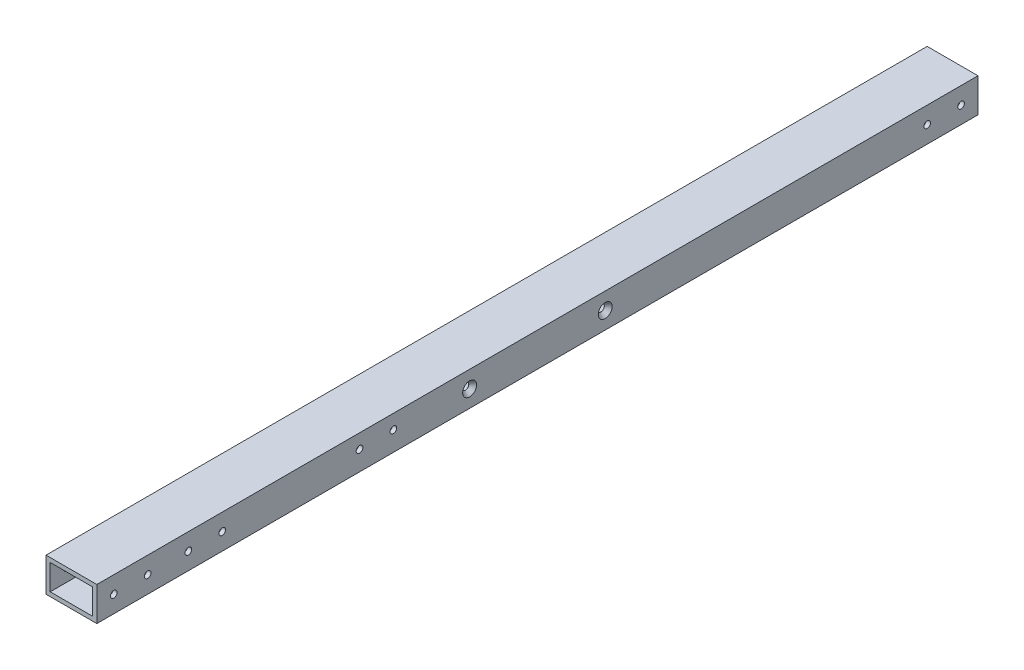
SolidWorks part; units mm, degrees
material "1060 Alloy"
ref_plane "Front Plane" through (0, 0, 0) normal (0, 0, 1) x (1, 0, 0)
ref_plane "Top Plane" through (0, 0, 0) normal (0, 1, 0) x (1, 0, 0)
ref_plane "Right Plane" through (0, 0, 0) normal (1, 0, 0) x (0, 0, -1)
sketch "Sketch1" plane through (0, 0, 0) normal (0, 0, 1) x (1, 0, 0)
  line L0 (-15.875, 9.525) -> (15.875, 9.525)
  line L2 (-19.05, 12.7) -> (19.05, 12.7)
  line L3 (-19.05, 12.7) -> (-19.05, -12.7)
  line L4 (-19.05, -12.7) -> (19.05, -12.7)
  line L5 (19.05, 12.7) -> (19.05, -12.7)
  line L10 (15.875, 9.525) -> (15.875, -9.525)
  line L11 (-15.875, -9.525) -> (15.875, -9.525)
  line L12 (-15.875, 9.525) -> (-15.875, -9.525)
  point P12 (0, 12.7)
  point P14 (19.05, 0)
  dimension "Wall Thickness" = 3.175
  dimension "Outside Width" = 38.1
  dimension "Outside Height" = 25.4
  dimension "Inside Height" = 19.05
  dimension "Inside Width" = 31.75
sketch "Sketch2" plane through (0, 0, 0) normal (1, 0, 0) x (0, 0, -1)
  line L0 (330.2, 0) -> (-330.2, 0)
  point P4 (0, 0)
  point P7 (-330.2, 0)
  point P10 (330.2, 0)
  dimension "Length" = 660.4
sketch "Sketch3" plane through (0, 0, 0) normal (0, 0, 1) x (1, 0, 0)
  line L21 (19.05, 12.7) -> (-19.05, 12.7)
  line L22 (19.05, -12.7) -> (19.05, 12.7)
  line L23 (-19.05, -12.7) -> (19.05, -12.7)
  line L24 (-19.05, 12.7) -> (-19.05, -12.7)
  line L25 (19.05, 12.7) -> (-19.05, 12.7)
  line L26 (19.05, -12.7) -> (19.05, 12.7)
  line L27 (-19.05, -12.7) -> (19.05, -12.7)
  line L28 (-19.05, 12.7) -> (-19.05, -12.7)
  line L29 (15.875, 9.525) -> (-15.875, 9.525)
  line L30 (15.875, -9.525) -> (15.875, 9.525)
  line L31 (-15.875, -9.525) -> (15.875, -9.525)
  line L32 (-15.875, 9.525) -> (-15.875, -9.525)
  line L33 (15.875, 9.525) -> (-15.875, 9.525)
  line L34 (15.875, -9.525) -> (15.875, 9.525)
  line L35 (-15.875, -9.525) -> (15.875, -9.525)
  line L36 (-15.875, 9.525) -> (-15.875, -9.525)
  dimension "D1" = 0
  dimension "D2" = 0
extrude "Boss-Extrude1" add sketch "Sketch3" along normal up to vertex (330.2 mm away) and the other way up to vertex (330.2 mm away) up to point (0, 0, 330.2) other way up to point (0, 0, -330.2)
sketch "Drawing Reference" plane through (0, 0, 0) normal (1, 0, 0) x (0, 0, -1)
  line L0 (-330.2, 0) -> (330.2, 0) construction
  line L1 (0, -12.7) -> (0, 12.7) construction
  line L2 (-330.2, -12.7) -> (330.2, -12.7) construction
  line L5 (-330.2, 12.7) -> (330.2, 12.7) construction
  point P7 (-302.768, 0)
  point P8 (302.768, 0)
  dimension "D1" = 27.432
sketch "Sketch4" plane through (-19.05, 0, 0) normal (-1, 0, 0) x (0, 0, 1)
  line L0 (-330.2, 0) -> (-317.5, 0)
  line L1 (-330.2, 12.7) -> (-330.2, -12.7) construction
  line L2 (-317.5, 0) -> (-292.1, 0)
  line L3 (330.2, 12.7) -> (330.2, -12.7) construction
  line L4 (330.2, 0) -> (317.5, 0)
  line L5 (317.5, 0) -> (292.1, 0)
  line L6 (0, 0) -> (50.8, 0) construction
  line L7 (0, 0) -> (-50.8, 0) construction
  point P11 (-317.5, 0)
  point P13 (-292.1, 0)
  point P14 (317.5, 0)
  point P15 (292.1, 0)
  point P17 (0, 0)
  point P19 (0, 0)
hole_wizard "#10 Clearance Hole2" positions "Sketch11" profile "Sketch12" hole size "#10" standard "ANSI Inch" end condition through all
sketch "Sketch11" plane through (-19.05, 0, 0) normal (-1, 0, 0) x (0, 0, 1)
  point P0 (-317.5, 0)
  point P3 (-292.1, 0)
  point P6 (292.1, 0)
  point P9 (317.5, 0)
sketch "Sketch12" plane through (-19.05, 0, -317.5) normal (0, 1, 0) x (0, 0, 1)
  line L0 (0, 0) -> (0, 38.1)
  line L1 (0, 38.1) -> (2.4892, 38.1)
  line L2 (2.4892, 38.1) -> (2.4892, 0)
  line L5 (2.4892, 0) -> (0, 0)
  line L11 (0, -6.35) -> (0, 107.95) construction
  dimension "Thru Hole Dia." = 4.9784
  dimension "Thru Hole Depth" = 38.1
hole_wizard "#10 Clearance Hole4" positions "Sketch14" profile "Sketch16" hole size "#10" standard "ANSI Inch" end condition through all
sketch "Sketch14" plane through (19.05, 0, 0) normal (1, 0, 0) x (0, 0, -1)
  point P33 (-261.6105, 0)
  point P36 (-236.2105, 0)
  point P42 (-133.3405, 1.9434)
  point P45 (-107.9405, 1.9434)
sketch "Sketch16" plane through (19.05, 0, 261.6105) normal (0, 1, 0) x (0, 0, -1)
  line L0 (0, 0) -> (0, 38.1)
  line L1 (0, 38.1) -> (2.4892, 38.1)
  line L2 (2.4892, 38.1) -> (2.4892, 0)
  line L5 (2.4892, 0) -> (0, 0)
  line L11 (0, -6.35) -> (0, 107.95) construction
  dimension "Thru Hole Dia." = 4.9784
  dimension "Thru Hole Depth" = 38.1
sketch "Sketch17" plane through (19.05, 0, 0) normal (1, 0, 0) x (0, 0, -1)
  point P0 (-261.8407, 0)
  point P1 (-236.4407, 0)
hole_wizard "#10 Clearance Hole3" positions "Sketch20" profile "Sketch21" hole size "#10" standard "ANSI Inch" end condition through all
sketch "Sketch20" plane through (-19.05, 0, 0) normal (-1, 0, 0) x (0, 0, 1)
  point P0 (-50.8, 0)
  point P3 (50.8, 0)
sketch "Sketch21" plane through (-19.05, 0, -50.8) normal (0, 1, 0) x (0, 0, 1)
  line L0 (0, 0) -> (0, 38.1)
  line L1 (0, 38.1) -> (5.207, 38.1)
  line L2 (2.4892, 34.9735) -> (2.4892, 0)
  line L5 (2.4892, 0) -> (0, 0)
  line L7 (5.207, 38.1) -> (2.4892, 34.9735)
  line L8 (-5.207, 38.1) -> (-2.4892, 34.9735) construction
  line L11 (0, -6.35) -> (0, 107.95) construction
  dimension "Thru Hole Dia." = 4.9784
  dimension "Thru Hole Depth" = 38.1
  dimension "Far C'Sink Dia." = 10.414
  dimension "Far C'Sink Angle" = 82
equation "\"D1@Drawing Reference\"=\"Outside Width@Sketch1\" * 0.72"
